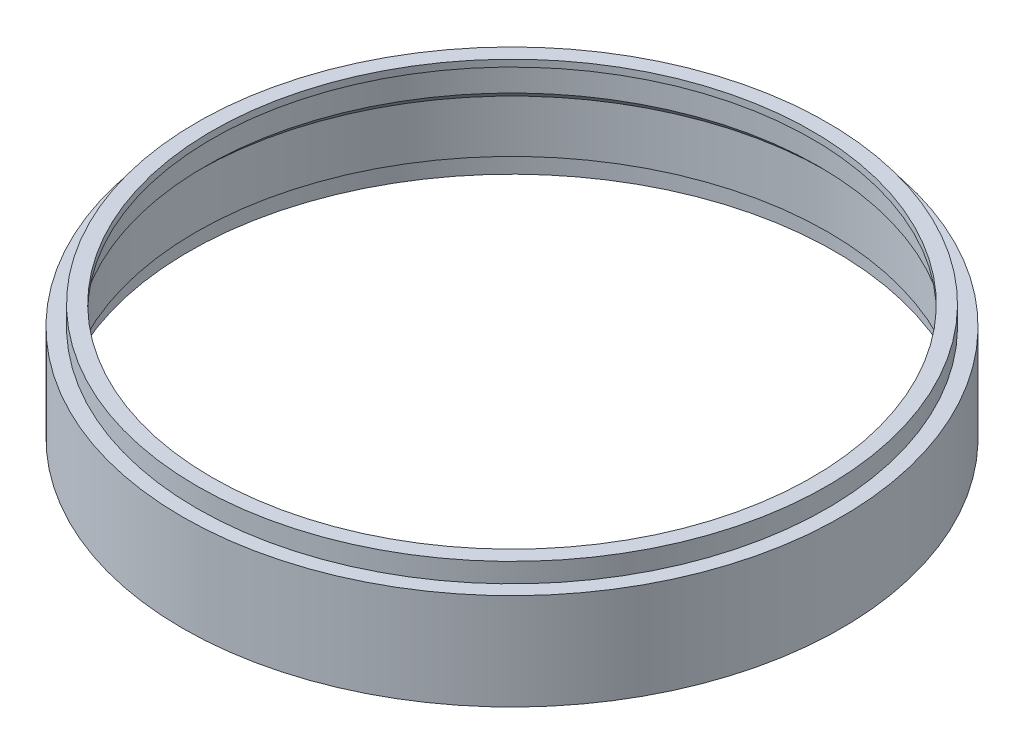
SolidWorks part; units mm, degrees
ref_plane "Front Plane" through (0, 0, 0) normal (0, 0, 1) x (1, 0, 0)
ref_plane "Top Plane" through (0, 0, 0) normal (0, 1, 0) x (1, 0, 0)
ref_plane "Right Plane" through (0, 0, 0) normal (1, 0, 0) x (0, 0, -1)
ref_axis "Axis1" through (0, 0, 0) along (0, 1, 0)
sketch "Sketch1" plane through (0, 0, 0) normal (0, 0, 1) x (1, 0, 0)
  line L0 (0, 0) -> (0, -50000) construction
  line L1 (-48.35, 0) -> (-48.35, 14.15)
  line L2 (-48.35, 0) -> (-47.4, 0)
  line L3 (-47.4, 0) -> (-47.4, 3)
  line L4 (-47.4, 3) -> (-46.35, 3)
  line L5 (-46.35, 3) -> (-46.35, 10.67)
  line L7 (-48.35, 0) -> (-48.35, -9.6235) construction
  line L8 (-46.35, 10.67) -> (-45.02, 12)
  line L10 (-45.02, 12) -> (-45.02, 16)
  line L11 (-45.02, 16) -> (-44.02, 16)
  line L12 (-47.35, 3) -> (-47.35, 0) construction
  line L13 (-46.35, 3) -> (-46.35, -7.15) construction
  line L14 (-45, 16.65) -> (-45, 12.65) construction
  line L17 (-44.02, 16) -> (-44.02, 17)
  line L26 (-46.22, 17) -> (-46.22, 14.15)
  line L27 (-46.22, 14.15) -> (-48.35, 14.15)
  line L31 (46.35, 3) -> (-46.35, 3) construction
  line L32 (-46.22, 17) -> (-44.02, 17)
  line L34 (-48.35, 15.15) -> (48.35, 15.15) construction
  dimension "D1" = 135
  dimension "D2" = 0.02
  dimension "D3" = 1.2
  dimension "D4" = 1
  dimension "D5" = 1
  dimension "D6" = 0.05
  dimension "D7" = 4
  dimension "D8" = 1
revolve "Revolve1" add sketch "Sketch1" angle 360 about L0
